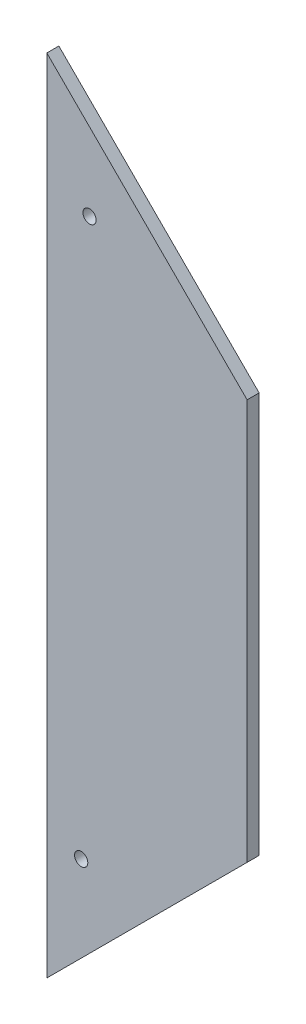
SolidWorks part; units mm, degrees
material "Сосна"
ref_plane "Спереди" through (0, 0, 0) normal (0, 0, 1) x (1, 0, 0)
ref_plane "Сверху" through (0, 0, 0) normal (0, 1, 0) x (1, 0, 0)
ref_plane "Справа" through (0, 0, 0) normal (1, 0, 0) x (0, 0, -1)
sketch "Эскиз1" plane through (0, 0, 0) normal (0, 0, 1) x (1, 0, 0)
  line L0 (0, 0) -> (0, 200)
  line L1 (0, 0) -> (50, 50)
  line L2 (50, 50) -> (50, 150)
  line L3 (50, 150) -> (0, 200)
  dimension "D1" = 200
  dimension "D2" = 50
  dimension "D3" = 45
  dimension "D4" = 45
extrude "Бобышка-Вытянуть1" add sketch "Эскиз1" along normal blind 3
sketch "Эскиз3" plane through (0, 0, 0) normal (-1, 0, 0) x (0, 0, 1)
  line L0 (1.5, 200) -> (1.5, -113.6649) construction
  line L1 (3, 200) -> (0, 200) construction
sketch "Эскиз4" plane through (50, 0, 0) normal (1, 0, 0) x (0, 0, -1)
  line L0 (-1.5, 150) -> (-1.5, -28.0184) construction
  line L1 (-3, 150) -> (0, 150) construction
extrude "Вырез-Вытянуть1" cut sketch "Эскиз5" against normal blind 8 contours L4 A0 | A0 L4 | A1 region at (9.955, 170.0104, -1.5) region at (11.3554, 169.9896, -1.5) region at (8.5714, 30.0155, -1.5)
sketch "Эскиз5" plane through (-305.9612, -184.2045, -1.5) normal (0, 0, -1) x (-0.9999, 0.0149, 0)
  line L0 (-300.2088, 388.7158) -> (-304.8774, 75.0857) construction
  line L2 (-317.5586, 363.9713) -> (-305.06, 363.7853)
  line L3 (-317.7074, 353.9725) -> (-305.2088, 353.7864)
  line L4 (-311.3093, 363.8783) -> (-311.3093, 353.8772) construction
  circle A0 centre (-311.3093, 358.8778) radius 1.65
  circle A1 centre (-311.3093, 218.8778) radius 1.65
  dimension "D1" = 10.6552
  dimension "D2" = 29.8381
  dimension "D3" = 2
